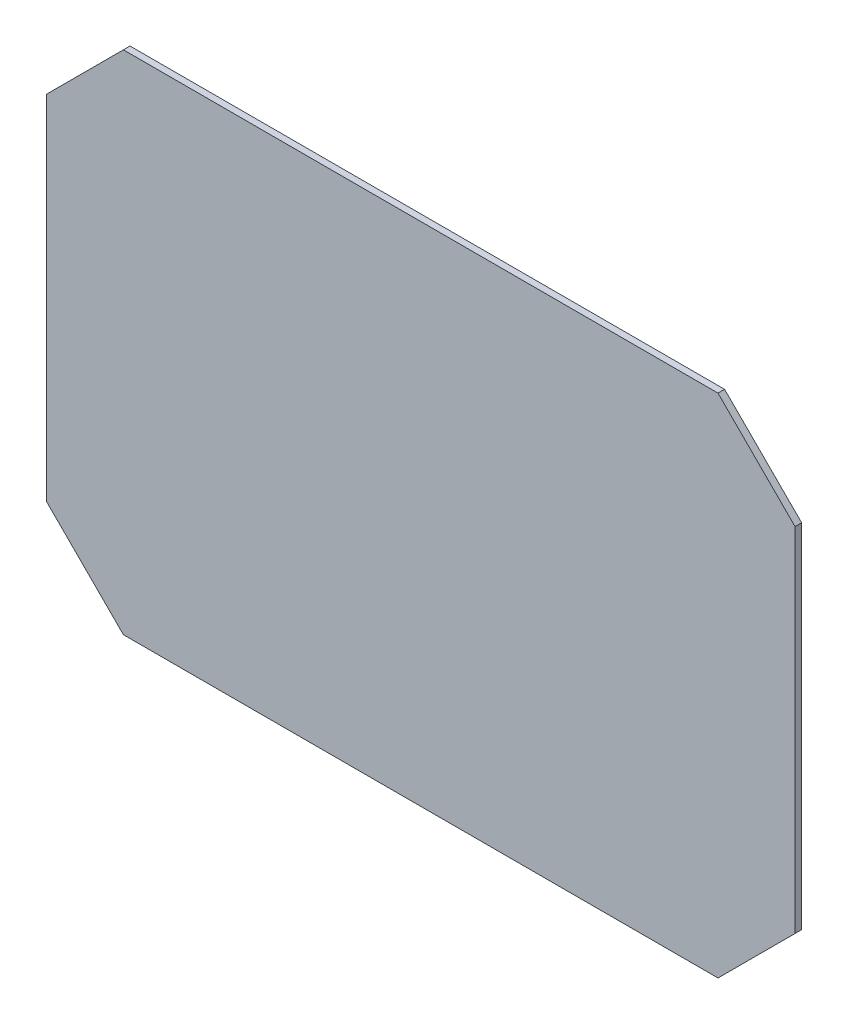
SolidWorks part; units mm, degrees
ref_plane "Front Plane" through (0, 0, 0) normal (0, 0, 1) x (1, 0, 0)
ref_plane "Top Plane" through (0, 0, 0) normal (0, 1, 0) x (1, 0, 0)
ref_plane "Right Plane" through (0, 0, 0) normal (1, 0, 0) x (0, 0, -1)
sketch "Sketch1" plane through (0, 0, 0) normal (0, 0, 1) x (1, 0, 0)
  line L1 (-170, 115) -> (170, 115)
  line L2 (-170, 115) -> (-170, -115)
  line L3 (-170, -115) -> (170, -115)
  line L4 (170, 115) -> (170, -115)
  line L5 (-170, 115) -> (170, -115) construction
  line L6 (-170, -115) -> (170, 115) construction
  point P0 (0, 0)
  dimension "D1" = 230
  dimension "D2" = 340
extrude "Boss-Extrude1" add sketch "Sketch1" along normal blind 3
chamfer "Chamfer1" [suppressed] distance 35 angle 45
chamfer "Chamfer2" distance 35 angle 45 4 edges at (170, -115, 1.5) (170, 115, 1.5) (-170, -115, 1.5) (-170, 115, 1.5)
